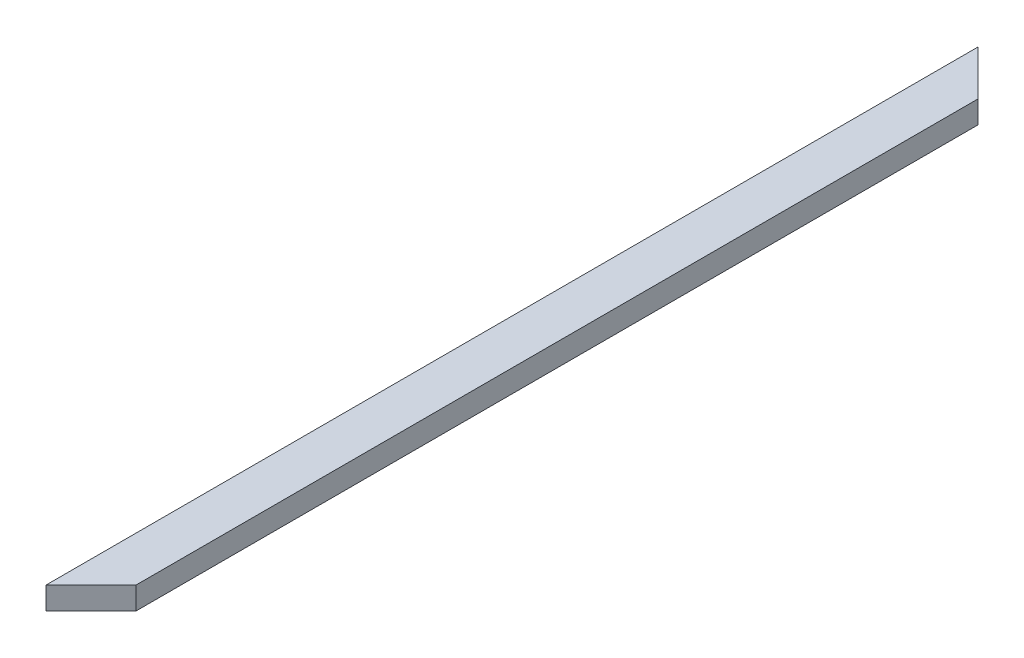
SolidWorks part; units mm, degrees
ref_plane "Front Plane" through (0, 0, 0) normal (0, 0, 1) x (1, 0, 0)
ref_plane "Top Plane" through (0, 0, 0) normal (0, 1, 0) x (1, 0, 0)
ref_plane "Right Plane" through (0, 0, 0) normal (1, 0, 0) x (0, 0, -1)
sketch "Sketch1" plane through (0, 0, 0) normal (0, 0, 1) x (1, 0, 0)
  line L1 (0, 0) -> (14, 0)
  line L2 (0, 0) -> (0, 7)
  line L3 (0, 7) -> (14, 7)
  line L4 (14, 0) -> (14, 7)
  dimension "D1" = 7
  dimension "D2" = 14
extrude "Boss-Extrude1" add sketch "Sketch1" along normal blind 290
sketch "Sketch2" plane through (0, 7, 0) normal (0, 1, 0) x (1, 0, 0)
  line L0 (0, 0) -> (14, -14)
  line L1 (14, -290) -> (14, 0) construction
  line L2 (14, -14) -> (14, 0)
  line L3 (14, 0) -> (0, 0)
  line L4 (14, -145) -> (0, -145) construction
  line L5 (0, -290) -> (0, 0) construction
  line L6 (14, -290) -> (0, -290)
  line L7 (14, -276) -> (14, -290)
  line L8 (0, -290) -> (14, -276)
  dimension "D1" = 45
extrude "Cut-Extrude1" cut sketch "Sketch2" against normal through all
